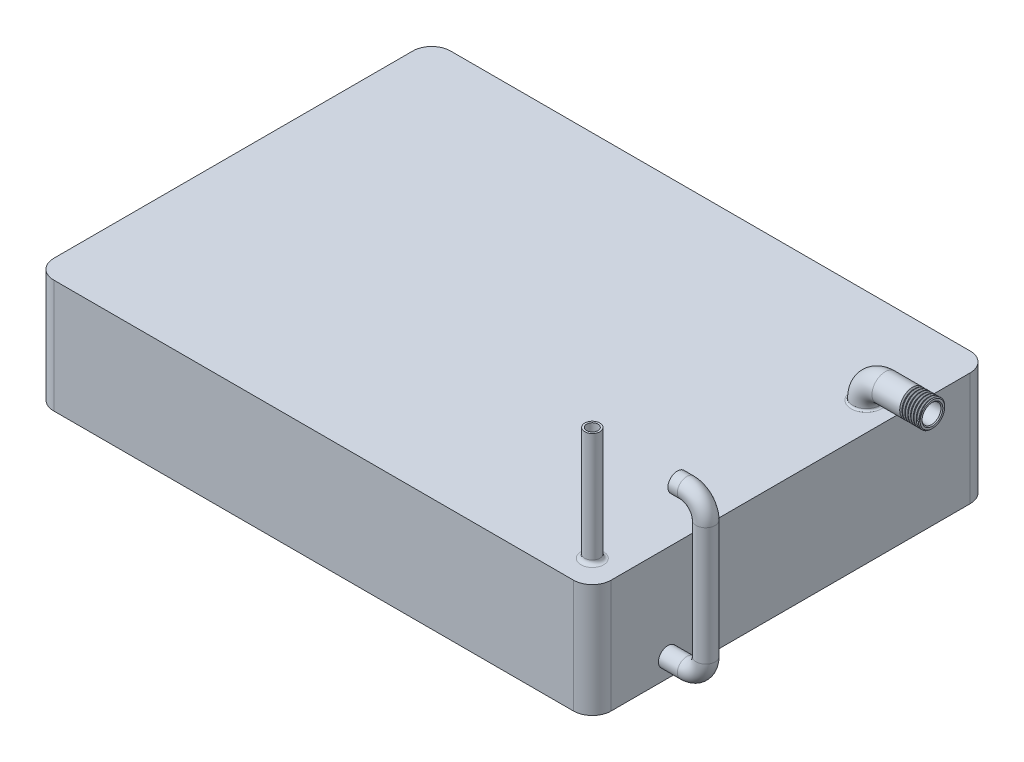
SolidWorks part; units mm, degrees
material "Galvanized Steel"
ref_plane "Front Plane" through (0, 0, 0) normal (0, 0, 1) x (1, 0, 0)
ref_plane "Top Plane" through (0, 0, 0) normal (0, 1, 0) x (1, 0, 0)
ref_plane "Right Plane" through (0, 0, 0) normal (1, 0, 0) x (0, 0, -1)
sketch "Sketch1" plane through (0, 0, 0) normal (0, 1, 0) x (1, 0, 0)
  line L1 (10, 0) -> (285, 0)
  line L2 (0, 10) -> (0, 200)
  line L3 (10, 210) -> (285, 210)
  line L4 (295, 10) -> (295, 200)
  arc A0 (10, 0) -> (0, 10) centre (10, 10) cw
  arc A1 (295, 10) -> (285, 0) centre (285, 10) cw
  arc A2 (295, 200) -> (285, 210) centre (285, 200) ccw
  arc A3 (10, 210) -> (0, 200) centre (10, 200) ccw
  point P7 (0, 0)
  point P10 (295, 0)
  point P13 (295, 210)
  point P16 (0, 210)
  dimension "D3" = 10
  dimension "D1" = 210
  dimension "D2" = 295
extrude "Boss-Extrude1" add sketch "Sketch1" along normal blind 60 contours L1 A1 L4 A2 L3 A3 L2 A0
sketch "Sketch3" plane through (0, 60, 0) normal (0, 1, 0) x (1, 0, 0)
  line L8 (10, 5) -> (285, 5)
  line L9 (290, 10) -> (290, 200)
  line L10 (285, 205) -> (10, 205)
  line L11 (5, 200) -> (5, 10)
  line L12 (10, 5) -> (285, 5)
  line L13 (290, 10) -> (290, 200)
  line L14 (285, 205) -> (10, 205)
  line L15 (5, 200) -> (5, 10)
  arc A8 (5, 10) -> (10, 5) centre (10, 10) ccw
  arc A9 (285, 5) -> (290, 10) centre (285, 10) ccw
  arc A10 (290, 200) -> (285, 205) centre (285, 200) ccw
  arc A11 (10, 205) -> (5, 200) centre (10, 200) ccw
  arc A12 (5, 10) -> (10, 5) centre (10, 10) ccw
  arc A13 (285, 5) -> (290, 10) centre (285, 10) ccw
  arc A14 (290, 200) -> (285, 205) centre (285, 200) ccw
  arc A15 (10, 205) -> (5, 200) centre (10, 200) ccw
  dimension "D1" = 5
extrude "Cut-Extrude1" cut sketch "Sketch3" against normal blind 50 from offset 5 offset against normal yes
sketch "Sketch4" plane through (0, 60, 0) normal (0, 1, 0) x (1, 0, 0)
  line L0 (10, 0) -> (285, 0) construction
  line L1 (295, 10) -> (295, 200) construction
  circle A0 centre (280, 15) radius 3
  dimension "D1" = 15
  dimension "D2" = 15
extrude "Cut-Extrude2" cut sketch "Sketch4" against normal blind 5 and the other way through all from surface starting at face at (147.5, 60, -105)
sketch "Sketch5" plane through (0, 60, 0) normal (0, 1, 0) x (1, 0, 0)
  line L0 (295, 10) -> (295, 200) construction
  line L1 (10, 210) -> (285, 210) construction
  circle A0 centre (280, 160) radius 5
  dimension "D1" = 15
  dimension "D2" = 50
extrude "Cut-Extrude3" cut sketch "Sketch5" against normal blind 10
sketch "Sketch6" plane through (0, 60, 0) normal (0, 1, 0) x (1, 0, 0)
  circle A1 centre (280, 160) radius 5
  circle A2 centre (280, 160) radius 7
  circle A3 centre (280, 160) radius 7
  dimension "D2" = 14
  dimension "D3" = 10
  dimension "D1" = 2
ref_plane "Plane1" through (0, 0, -195) normal (0, 0, -1) x (-1, 0, 0)
sketch "Sketch7" plane through (0, 0, -195) normal (0, 0, -1) x (-1, 0, 0)
  line L0 (-280, 60) -> (-280, 61)
  line L2 (-290, 71) -> (-315, 71)
  arc A0 (-280, 61) -> (-290, 71) centre (-290, 61) ccw
  point P5 (-280, 71)
  dimension "D1" = 11
  dimension "D3" = 10
  dimension "D2" = 35
sweep "Sweep6" add profiles "Sketch6" path "Sketch7"
sketch "Sketch8" plane through (0, 60, 0) normal (0, 1, 0) x (1, 0, 0)
  circle A0 centre (280, 15) radius 3
  circle A1 centre (280, 15) radius 4
extrude "Boss-Extrude2" add sketch "Sketch8" along normal blind 60
sketch "Sketch9" plane through (295, 0, 0) normal (1, 0, 0) x (0, 0, -1)
  line L0 (10, 0) -> (200, 0) construction
  line L1 (0, 60) -> (0, 0) construction
  circle A0 centre (40, 10) radius 4
  dimension "D1" = 8
  dimension "D2" = 10
  dimension "D3" = 40
fillet "Fillet2" radius 2 1 edges at (280, 60, -19)
extrude "Cut-Extrude4" cut sketch "Sketch9" against normal blind 5 contours A0
sketch "Sketch10" plane through (295, 0, 0) normal (1, 0, 0) x (0, 0, -1)
  circle A1 centre (40, 10) radius 5
  circle A2 centre (40, 10) radius 4
  circle A3 centre (40, 10) radius 4
  dimension "D3" = 10
  dimension "D1" = 0
  dimension "D2" = 1
ref_plane "Plane2" through (0, 0, -40) normal (0, 0, 1) x (1, 0, 0)
sketch "Sketch11" plane through (0, 0, -40) normal (0, 0, 1) x (1, 0, 0)
  line L0 (295, 10) -> (305, 10)
  line L1 (295, 5) -> (295, 15) construction
  line L2 (315, 20) -> (315, 82.5)
  line L3 (305, 92.5) -> (300, 92.5)
  arc A0 (305, 10) -> (315, 20) centre (305, 20) ccw
  arc A1 (315, 82.5) -> (305, 92.5) centre (305, 82.5) ccw
  point P8 (315, 10)
  point P11 (315, 80)
  dimension "D4" = 10
  dimension "D1" = 20
  dimension "D2" = 70
  dimension "D3" = 5
  dimension "D5" = 62.5
sweep "Sweep7" add profiles "Sketch10" path "Sketch11"
fillet "Fillet3" radius 1 1 edges at (280, 60, -153)
thread "Thread1" pitch 1.5 method cut profile "Thread Profile1" start angle 0, offset 0, length 10, pitch 1.5, diameter 14
ref_plane "Plane3" through (315, 71, -153) normal (0, -1, 0) x (0, 0, 1)
sketch "Thread Profile1" plane through (315, 71, -153) normal (0, -1, 0) x (0, 0, 1)
  line L0 (0, 0) -> (0, 1.5) construction
  line L11 (0, 0) -> (0, 1.3125)
  line L12 (0, 1.3125) -> (-0.8119, 0.8437)
  line L13 (-0.8119, 0.8437) -> (-0.8119, 0.4687)
  line L15 (-0.8119, 0.4687) -> (0, 0)
  line L17 (-0.8119, 0.6562) -> (0, 0.6562) construction
  point P2 (0, 0)
  dimension "Pitch" = 1.5
  dimension "Profile_Angle" = 60
  dimension "Profile_Land" = 0.375
  dimension "Profile_Height" = 0.8119
chamfer "Chamfer1" distance 0.5 angle 45 2 edges at (315, 71, -153) (315, 71, -155)
